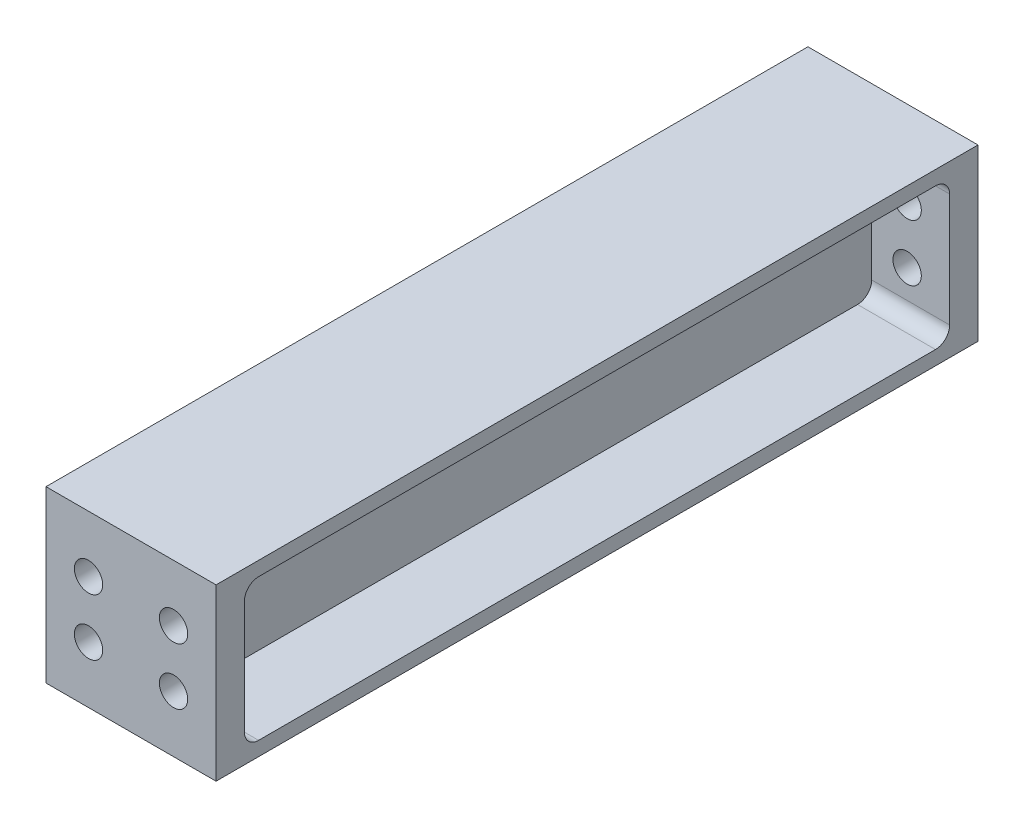
SolidWorks part; units mm, degrees
material "6061 Alloy"
ref_plane "Front Plane" through (0, 0, 0) normal (0, 0, 1) x (1, 0, 0)
ref_plane "Top Plane" through (0, 0, 0) normal (0, 1, 0) x (1, 0, 0)
ref_plane "Right Plane" through (0, 0, 0) normal (1, 0, 0) x (0, 0, -1)
sketch "Sketch2" plane through (0, 0, 0) normal (0, 0, 1) x (1, 0, 0)
  line L1 (0, 0) -> (38.1, 0)
  line L2 (0, 0) -> (0, 38.1)
  line L3 (0, 38.1) -> (38.1, 38.1)
  line L4 (38.1, 0) -> (38.1, 38.1)
  dimension "D1" = 38.1
extrude "Boss-Extrude1" add sketch "Sketch2" along normal up to surface (170.686 mm away)
ref_plane "Plane1" through (19.05, 0, 0) normal (1, 0, 0) x (0, 0, -1)
sketch "Sketch3" plane through (38.1, 0, 0) normal (1, 0, 0) x (0, 0, -1)
  line L4 (-85.343, 34.925) -> (-85.343, 38.1) construction
  line L5 (-164.336, 34.925) -> (-6.35, 34.925)
  line L6 (-164.336, 34.925) -> (-164.336, 3.175)
  line L7 (-164.336, 3.175) -> (-6.35, 3.175)
  line L8 (-6.35, 34.925) -> (-6.35, 3.175)
  line L9 (-170.686, 38.1) -> (0, 38.1) construction
  line L10 (-6.35, 19.05) -> (0, 19.05) construction
  line L11 (0, 0) -> (0, 38.1) construction
  dimension "D1" = 6.35
  dimension "D2" = 3.175
extrude "Cut-Extrude1" cut sketch "Sketch3" against normal blind 17.4625
fillet "Fillet1" radius 3.175 4 edges at (29.3688, 3.175, 6.35) (29.3688, 3.175, 164.336) (29.3688, 34.925, 164.336) (29.3688, 34.925, 6.35)
mirror "Mirror1" about plane through (19.05, 0, 0) normal (1, 0, 0) of "Fillet1", "Cut-Extrude1"
hole_wizard "1/4 (0.25) Diameter Hole1" positions "Sketch5" profile "Sketch6" hole size "1/4" standard "ANSI Inch" end condition through all
sketch "Sketch5" plane through (0, 0, 0) normal (0, 0, -1) x (-1, 0, 0)
  line L0 (0, 38.1) -> (0, 0) construction
  line L1 (-38.1, 0) -> (-38.1, 38.1) construction
  line L2 (-38.1, 38.1) -> (0, 38.1) construction
  line L3 (0, 0) -> (-38.1, 0) construction
  point P0 (-9.525, 25.4)
  point P2 (-9.525, 12.7)
  point P4 (-28.575, 12.7)
  point P6 (-28.575, 25.4)
  dimension "D1" = 9.525
  dimension "D2" = 9.525
  dimension "D3" = 12.7
  dimension "D4" = 12.7
sketch "Sketch6" plane through (9.525, 25.4, 0) normal (1, 0, 0) x (0, 1, 0)
  line L0 (0, 0) -> (0, 170.686)
  line L1 (0, 170.686) -> (3.175, 170.686)
  line L2 (3.175, 170.686) -> (3.175, 0)
  line L5 (3.175, 0) -> (0, 0)
  line L11 (0, -6.35) -> (0, 107.95) construction
  dimension "Thru Hole Dia." = 6.35
  dimension "Thru Hole Depth" = 170.686
